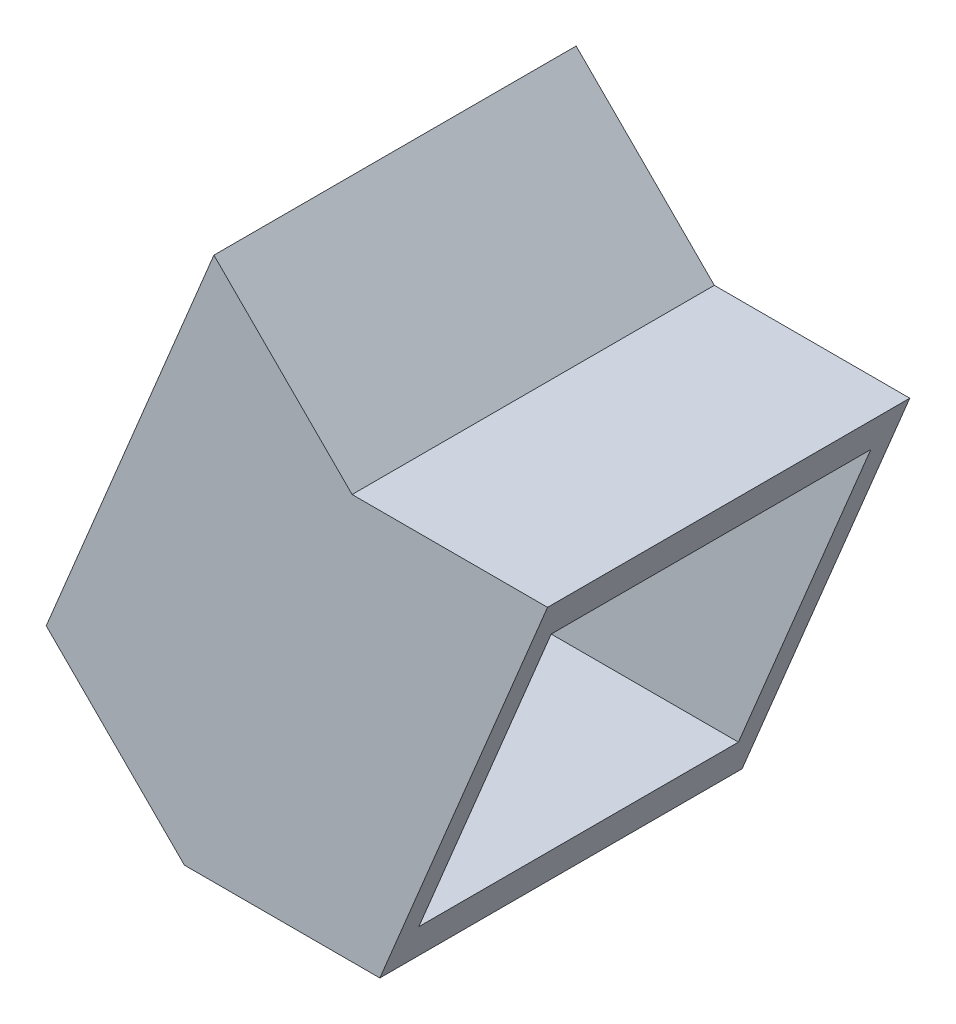
SolidWorks part; units mm, degrees
ref_plane "Plano frontal" through (0, 0, 0) normal (0, 0, 1) x (1, 0, 0)
ref_plane "Plano superior" through (0, 0, 0) normal (0, 1, 0) x (1, 0, 0)
ref_plane "Plano direito" through (0, 0, 0) normal (1, 0, 0) x (0, 0, -1)
sketch "Esboço1" plane through (0, 0, 0) normal (0, 0, 1) x (1, 0, 0)
  line L1 (184, 76.2153) -> (76.2153, 184)
  line L2 (76.2153, 184) -> (-76.2153, 184)
  line L3 (-76.2153, 184) -> (-184, 76.2153)
  line L4 (-184, 76.2153) -> (-184, -76.2153)
  line L5 (-184, -76.2153) -> (-76.2153, -184)
  line L6 (-76.2153, -184) -> (76.2153, -184)
  line L7 (76.2153, -184) -> (184, -76.2153)
  line L8 (184, -76.2153) -> (184, 76.2153)
  line L9 (146, 60.4752) -> (60.4752, 146)
  line L10 (60.4752, 146) -> (-60.4752, 146)
  line L11 (-60.4752, 146) -> (-146, 60.4752)
  line L12 (-146, 60.4752) -> (-146, -60.4752)
  line L13 (-146, -60.4752) -> (-60.4752, -146)
  line L14 (-60.4752, -146) -> (60.4752, -146)
  line L15 (60.4752, -146) -> (146, -60.4752)
  line L16 (146, -60.4752) -> (146, 60.4752)
  line L17 (180, 74.5584) -> (74.5584, 180)
  line L18 (74.5584, 180) -> (-74.5584, 180)
  line L19 (-74.5584, 180) -> (-180, 74.5584)
  line L20 (-180, 74.5584) -> (-180, -74.5584)
  line L21 (-180, -74.5584) -> (-74.5584, -180)
  line L22 (-74.5584, -180) -> (74.5584, -180)
  line L23 (74.5584, -180) -> (180, -74.5584)
  line L24 (180, -74.5584) -> (180, 74.5584)
  line L25 (150, 62.132) -> (62.132, 150)
  line L26 (62.132, 150) -> (-62.132, 150)
  line L27 (-62.132, 150) -> (-150, 62.132)
  line L28 (-150, 62.132) -> (-150, -62.132)
  line L29 (-150, -62.132) -> (-62.132, -150)
  line L30 (-62.132, -150) -> (62.132, -150)
  line L31 (62.132, -150) -> (150, -62.132)
  line L32 (150, -62.132) -> (150, 62.132)
  circle A0 centre (0, 0) radius 184 construction
  circle A1 centre (0, 0) radius 146 construction
  circle A2 centre (0, 0) radius 180 construction
  circle A3 centre (0, 0) radius 150 construction
extrude "Ressalto-extrusão1" add sketch "Esboço1" along normal blind 34 contours L7 L8 L1 L2 L3 L4 L5 L6 L24 L23 L22 L21 L20 L19 L18 L17 | L31 L32 L25 L26 L27 L28 L29 L30 L16 L15 L14 L13 L12 L11 L10 L9 region at (183.4796, 0, 0) region at (149.5757, 0, 0)
extrude "Ressalto-extrusão2" add sketch "Esboço1<3>" along normal blind 2 contours L23 L24 L17 L18 L19 L20 L21 L22 L32 L31 L30 L29 L28 L27 L26 L25 region at (174.9088, 0, 0)
sketch "Esboço1<3>" plane through (0, 0, 0) normal (0, 0, 1) x (1, 0, 0) same geometry as "Esboço1"
extrude "Ressalto-extrusão3" add sketch "Esboço1<4>" against normal blind 2 from surface contours L23 L24 L17 L18 L19 L20 L21 L22 L32 L31 L30 L29 L28 L27 L26 L25 region at (174.9088, 0, 0) starting at face at (0, 0, 34)
sketch "Esboço1<4>" plane through (0, 0, 0) normal (0, 0, 1) x (1, 0, 0) same geometry as "Esboço1"
sketch "Esboço5" plane through (0, 0, 34) normal (0, 0, 1) x (1, 0, 0)
  line L0 (-76.2153, -184) -> (-60.4752, -146)
  line L1 (-76.2153, -184) -> (-57.8721, -184)
  line L2 (-60.4752, -146) -> (-42.132, -146)
  line L3 (-57.8721, -184) -> (-42.132, -146)
  line L4 (-60.4752, -146) -> (60.4752, -146) construction
  line L5 (-76.2153, -184) -> (-60.4752, -146)
  line L6 (-76.2153, -184) -> (-89.1859, -171.0294)
  line L7 (-60.4752, -146) -> (-73.4457, -133.0294)
  line L8 (-89.1859, -171.0294) -> (-73.4457, -133.0294)
  line L9 (-146, -60.4752) -> (-60.4752, -146) construction
  line M5 (146, 60.4752) -> (146, -60.4752)
  line M6 (146, -60.4752) -> (60.4752, -146)
  line M7 (60.4752, -146) -> (-60.4752, -146)
  line M8 (-60.4752, -146) -> (-146, -60.4752)
  line M9 (-146, -60.4752) -> (-146, 60.4752)
  line M10 (-146, 60.4752) -> (-60.4752, 146)
  line M11 (-60.4752, 146) -> (60.4752, 146)
  line M12 (60.4752, 146) -> (146, 60.4752)
  line M13 (76.2153, -184) -> (184, -76.2153)
  line M14 (184, -76.2153) -> (184, 76.2153)
  line M15 (184, 76.2153) -> (76.2153, 184)
  line M16 (76.2153, 184) -> (-76.2153, 184)
  line M17 (-76.2153, 184) -> (-184, 76.2153)
  line M18 (-184, 76.2153) -> (-184, -76.2153)
  line M19 (-184, -76.2153) -> (-76.2153, -184)
  line M20 (-76.2153, -184) -> (76.2153, -184)
extrude "Corte-extrusão2" cut sketch "Esboço5" against normal blind 42 contours L8 L3 M19 M8 M9 M10 M11 M12 M5 M6 M7 M20 M13 M14 M15 M16 M17 M18 region at (-45.1939, -166.9916, 34)
sketch "Esboço6" plane through (0, 0, 34) normal (0, 0, 1) x (1, 0, 0)
  circle A0 centre (-74.8305, -158.5147) radius 3.5
  circle A1 centre (-59.1737, -165) radius 3.5
